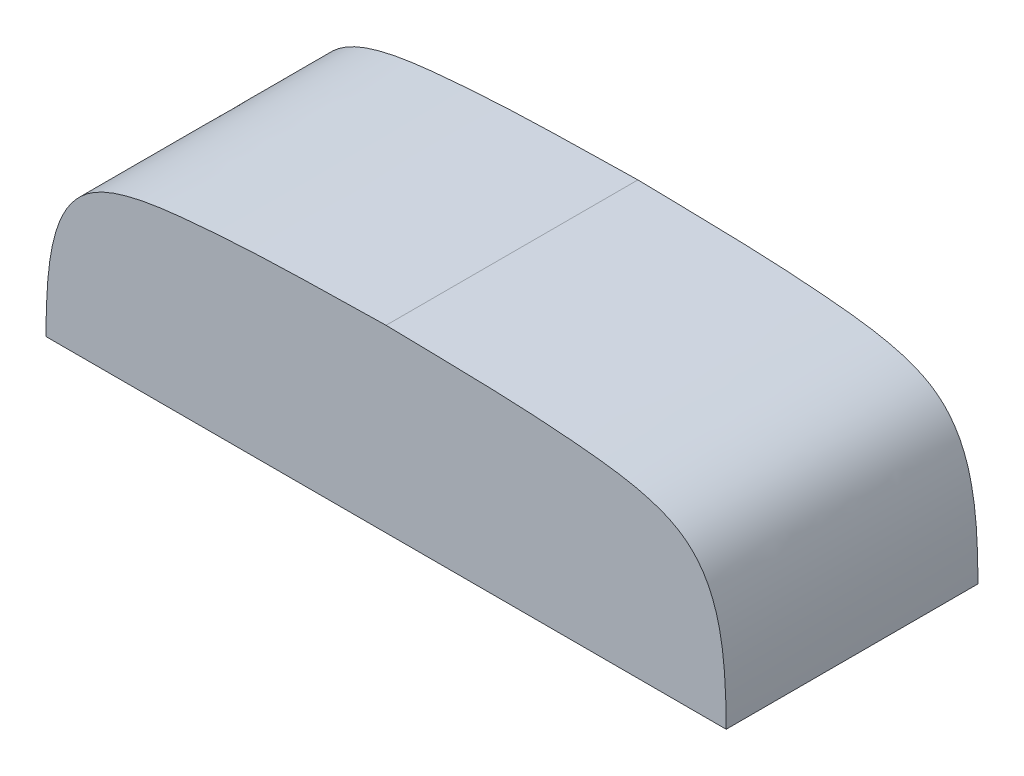
SolidWorks part; units mm, degrees
ref_plane "Front Plane" through (0, 0, 0) normal (0, 0, 1) x (1, 0, 0)
ref_plane "Top Plane" through (0, 0, 0) normal (0, 1, 0) x (1, 0, 0)
ref_plane "Right Plane" through (0, 0, 0) normal (1, 0, 0) x (0, 0, -1)
sketch "Sketch1" plane through (0, 0, 0) normal (0, 0, 1) x (1, 0, 0)
  line L2 (0, 265.0008) -> (0, -43.3016) construction
  line L3 (343.0467, 50.8638) -> (-343.0467, 50.8638)
  spline S0 degree 3 poles (0, 232.2583) (64.9766, 230.6298) (157.6161, 231.0971) (335.026, 207.3029) (342.768, 116.1788) (343.0467, 50.8638) knots 0 0 0 0 0.225226 0.33784 0.524743 0.524743 0.524743 0.524743
  spline S1 degree 3 poles (0, 232.2583) (-64.9766, 230.6298) (-157.6161, 231.0971) (-335.026, 207.3029) (-342.768, 116.1788) (-343.0467, 50.8638) knots 0 0 0 0 0.225226 0.33784 0.524743 0.524743 0.524743 0.524743
  point P8 (0, 0.0638)
  dimension "D2" = 50.8
extrude "Boss-Extrude1" add sketch "Sketch1" along normal blind 127 and the other way blind 127
